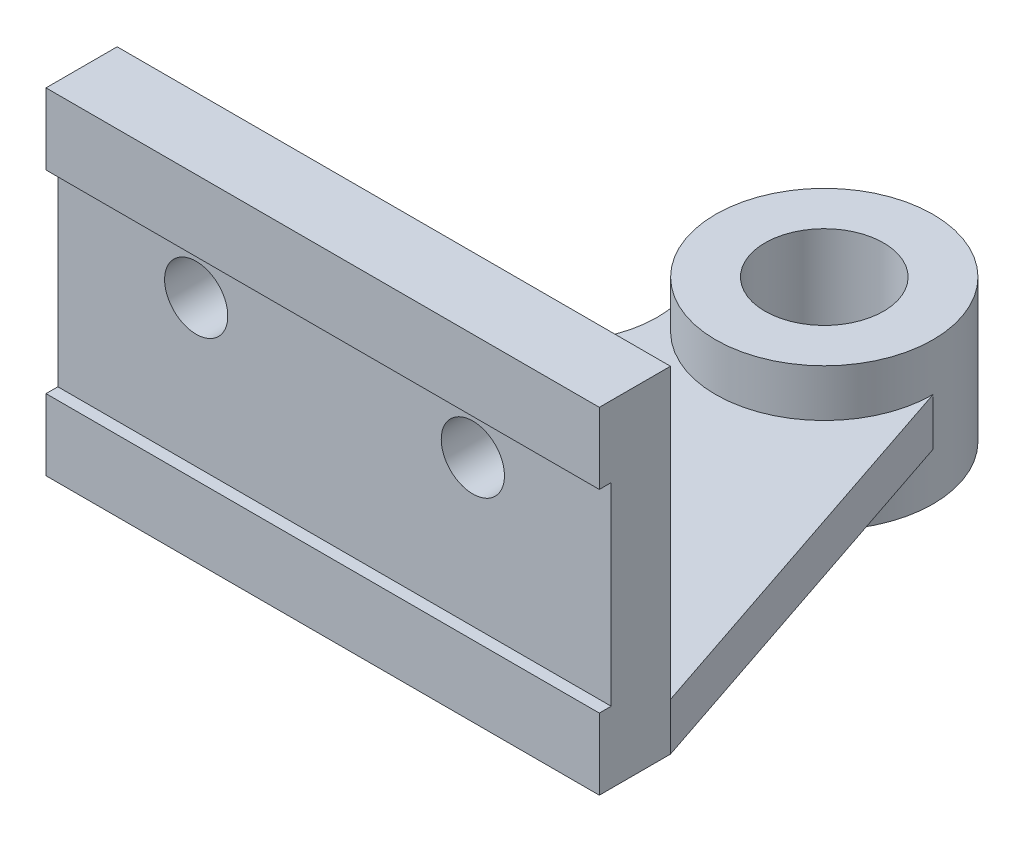
SolidWorks part; units mm, degrees
ref_plane "Front Plane" through (0, 0, 0) normal (0, 0, 1) x (1, 0, 0)
ref_plane "Top Plane" through (0, 0, 0) normal (0, 1, 0) x (1, 0, 0)
ref_plane "Right Plane" through (0, 0, 0) normal (1, 0, 0) x (0, 0, -1)
sketch "Sketch1" plane through (0, 0, 0) normal (0, 1, 0) x (1, 0, 0)
  line L0 (-78.9198, -100) -> (61.0802, -100)
  line L1 (-78.9198, -62) -> (-78.9198, -100)
  line L2 (27.5, 0) -> (61.0802, -100)
  line L3 (-78.9198, -100) -> (-78.9198, -118)
  line L4 (-78.9198, -118) -> (61.0802, -118)
  line L5 (61.0802, -118) -> (61.0802, -100)
  circle A0 centre (0, 0) radius 15
  circle A1 centre (0, 0) radius 27.5
  circle A2 centre (-58.9198, -62) radius 9
  circle A3 centre (-58.9198, -62) radius 20
  arc A4 (-54.6459, -42.462) -> (-25.8256, -9.4493) centre (-49.3034, -18.0395) ccw
  dimension "D1" = 30
  dimension "D2" = 55
  dimension "D5" = 40
  dimension "D6" = 18
  dimension "D7" = 50
  dimension "D3" = 100
  dimension "D4" = 140
  dimension "D8" = 38
  dimension "D9" = 20
  dimension "D10" = 18
extrude "Boss-Extrude1" add sketch "Sketch1" along normal mid plane 36 contours A1 A0 region at (4.6625, 0, 26.3123)
extrude "Boss-Extrude2" add sketch "Sketch1<3>" along normal mid plane 12 contours A4 A3 L1 L0 L2 A1 region at (-1.7492, 0, 66.0576)
sketch "Sketch1<3>" plane through (0, 0, 0) normal (0, 1, 0) x (1, 0, 0) same geometry as "Sketch1"
extrude "Boss-Extrude3" add sketch "Sketch1<4>" along normal mid plane 36 contours A3 A2 region at (-71.1055, 0, 46.8606)
sketch "Sketch1<4>" plane through (0, 0, 0) normal (0, 1, 0) x (1, 0, 0) same geometry as "Sketch1"
sketch "Sketch2" plane through (0, -18, 0) normal (0, -1, 0) x (1, 0, 0)
  circle A0 centre (-58.9198, 62) radius 20
  circle A1 centre (-58.9198, 62) radius 9
extrude "Cut-Extrude1" cut sketch "Sketch2" against normal blind 12
extrude "Boss-Extrude4" add sketch "Sketch1<5>" along normal blind 79 contours L4 L5 L0 L3 region at (-8.9198, 0, 109)
sketch "Sketch1<5>" plane through (0, 0, 0) normal (0, 1, 0) x (1, 0, 0) same geometry as "Sketch1"
sketch "Sketch4" plane through (0, 0, 100) normal (0, 0, -1) x (-1, 0, 0)
  line L0 (78.9198, 79) -> (-61.0802, 79) construction
  line L1 (78.9198, 79) -> (78.9198, 6) construction
  line L2 (-61.0802, 79) -> (-61.0802, 6) construction
  circle A0 centre (-26.0802, 49) radius 8
  circle A1 centre (43.9198, 49) radius 8
  dimension "D1" = 16
  dimension "D2" = 16
  dimension "D3" = 30
  dimension "D4" = 35
  dimension "D5" = 30
  dimension "D6" = 35
extrude "Cut-Extrude2" cut sketch "Sketch4" against normal up to next
sketch "Sketch5" plane through (-78.9198, 0, 0) normal (-1, 0, 0) x (0, 0, 1)
  line L0 (118, 61) -> (115, 61)
  line L1 (118, 79) -> (118, 0) construction
  line L2 (115, 61) -> (115, 12)
  line L3 (115, 12) -> (118, 12)
  line L4 (100, 79) -> (118, 79) construction
  line L6 (118, 61) -> (118, 12)
  line L7 (62, -6) -> (100, -6) construction
  dimension "D1" = 18
  dimension "D2" = 18
  dimension "D3" = 3
extrude "Cut-Extrude3" cut sketch "Sketch5" against normal up to next
extrude "Boss-Extrude5" add sketch "Sketch1<6>" against normal blind 6 contours L4 L5 L0 L3 region at (-8.9198, 0, 109)
sketch "Sketch1<6>" plane through (0, 0, 0) normal (0, 1, 0) x (1, 0, 0) same geometry as "Sketch1"
